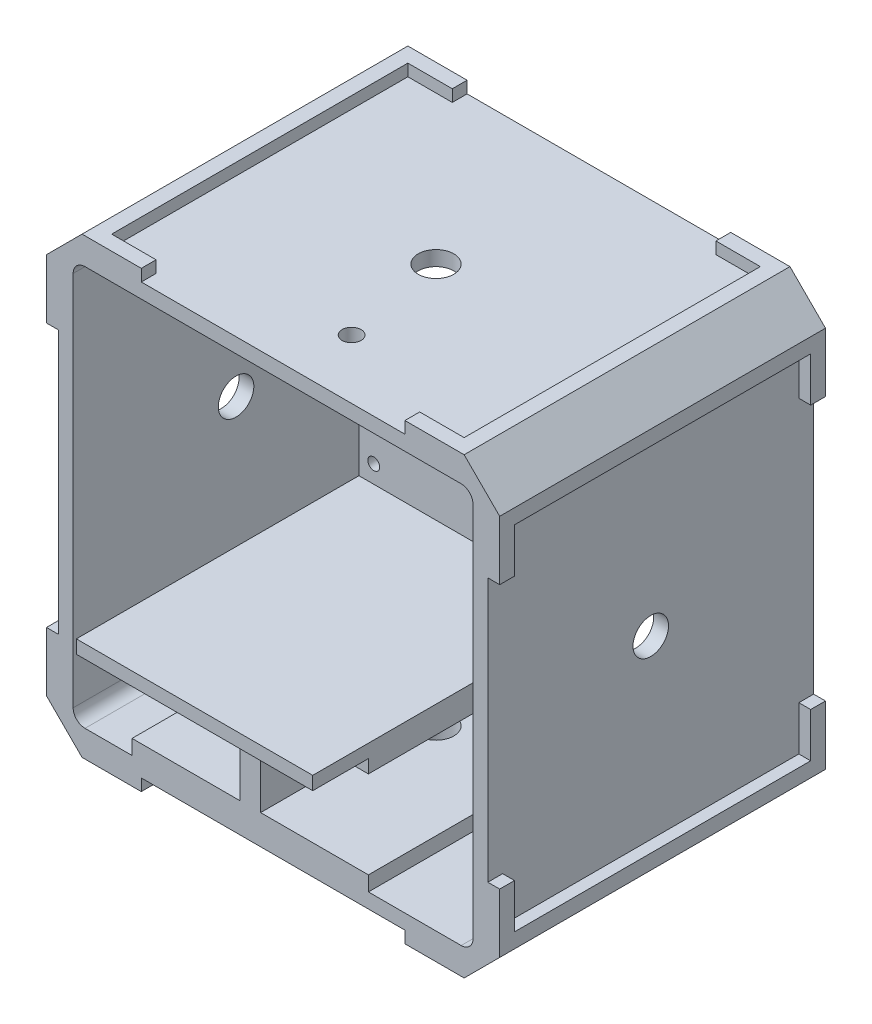
SolidWorks part; units mm, degrees
ref_plane "Front Plane" through (0, 0, 0) normal (0, 0, 1) x (1, 0, 0)
ref_plane "Top Plane" through (0, 0, 0) normal (0, 1, 0) x (1, 0, 0)
ref_plane "Right Plane" through (0, 0, 0) normal (1, 0, 0) x (0, 0, -1)
sketch "Sketch1" plane through (0, 0, 0) normal (0, 0, 1) x (1, 0, 0)
  line L0 (-33.75, -33.75) -> (33.75, -33.75) construction
  line L1 (-31.75, 33.75) -> (31.75, 33.75)
  line L2 (-33.75, 31.75) -> (-33.75, -31.75)
  line L3 (-31.75, -33.75) -> (31.75, -33.75)
  line L4 (33.75, 31.75) -> (33.75, -31.75)
  line L5 (-36.25, 32.25) -> (-36.25, -32.25)
  line L6 (33.75, 33.75) -> (33.75, -33.75) construction
  line L7 (-32.25, -36.25) -> (32.25, -36.25)
  line L8 (36.25, 32.25) -> (36.25, -32.25)
  line L9 (-32.25, 36.25) -> (32.25, 36.25)
  line L10 (-36.25, 36.25) -> (-36.25, -36.25) construction
  line L11 (-36.25, 36.25) -> (36.25, 36.25) construction
  line L12 (-33.75, 33.75) -> (33.75, 33.75) construction
  line L13 (-33.75, 33.75) -> (-33.75, -33.75) construction
  line L14 (-36.25, -36.25) -> (36.25, -36.25) construction
  line L15 (36.25, 36.25) -> (36.25, -36.25) construction
  line L16 (55, 0) -> (-55, 0) construction
  line L17 (0, -55) -> (0, 55) construction
  arc A0 (-36.25, 32.25) -> (-32.25, 36.25) centre (-32.25, 32.25) cw
  arc A1 (-31.75, 33.75) -> (-33.75, 31.75) centre (-31.75, 31.75) ccw
  arc A2 (-33.75, -31.75) -> (-31.75, -33.75) centre (-31.75, -31.75) ccw
  arc A3 (31.75, -33.75) -> (33.75, -31.75) centre (31.75, -31.75) ccw
  arc A4 (31.75, 33.75) -> (33.75, 31.75) centre (31.75, 31.75) cw
  arc A5 (-36.25, -32.25) -> (-32.25, -36.25) centre (-32.25, -32.25) ccw
  arc A6 (32.25, -36.25) -> (36.25, -32.25) centre (32.25, -32.25) ccw
  arc A7 (36.25, 32.25) -> (32.25, 36.25) centre (32.25, 32.25) ccw
  point P36 (-33.75, 0)
  point P39 (0, 33.75)
  dimension "D3" = 4
  dimension "D4" = 2
  dimension "D5" = 2
  dimension "D6" = 4
  dimension "D1" = 67.5
  dimension "D2" = 2.5
extrude "Boss-Extrude1" add sketch "Sketch1" along normal blind 55
sketch "Sketch2" plane through (0, 0, 0) normal (0, 0, 1) x (1, 0, 0)
  line L1 (-33.75, 33.75) -> (33.75, 33.75)
  line L2 (-33.75, 33.75) -> (-33.75, -33.75)
  line L3 (-33.75, -33.75) -> (33.75, -33.75)
  line L4 (33.75, 33.75) -> (33.75, -33.75)
extrude "Boss-Extrude2" add sketch "Sketch2" along normal blind 2.5
sketch "Sketch3" plane through (0, 0, 2.5) normal (0, 0, 1) x (1, 0, 0)
  line L0 (-4.38, 17.29) -> (-18.88, 12.29) construction
  line L1 (-19.88, 11.29) -> (-3.38, 11.29)
  line L2 (-18.88, 12.29) -> (-4.38, 12.29) construction
  line L3 (-18.88, 12.29) -> (-18.88, 17.29) construction
  line L4 (-18.88, 17.29) -> (-4.38, 17.29) construction
  line L5 (-4.38, 12.29) -> (-4.38, 17.29) construction
  line L6 (-3.38, 11.29) -> (-3.38, 18.29)
  line L7 (-19.88, 18.29) -> (-3.38, 18.29)
  line L8 (-19.88, 11.29) -> (-19.88, 18.29)
  line L9 (-36.25, 32.25) -> (-36.25, -32.25) construction
  line L10 (-3, -7) -> (3, -7) construction
  line L11 (-3, -7) -> (-3, 7) construction
  line L12 (-3, 7) -> (3, 7) construction
  line L13 (3, -7) -> (3, 7) construction
  line L14 (-3, -7) -> (3, 7) construction
  line L15 (-3, 7) -> (3, -7) construction
  line L16 (32.25, 36.25) -> (-32.25, 36.25) construction
  line L17 (-4, -8) -> (-4, 8)
  line L18 (-4, 8) -> (4, 8)
  line L19 (4, -8) -> (4, 8)
  line L20 (-4, -8) -> (4, -8)
  line L21 (-18.88, 17.29) -> (-4.38, 12.29) construction
  point P0 (0, 0)
  dimension "D2" = 6
  dimension "D3" = 14
  dimension "D5" = 14.5
  dimension "D6" = 5
  dimension "D7" = 16.37
  dimension "D8" = 23.96
  dimension "D1" = 1
  dimension "D4" = 1
extrude "Cut-Extrude1" cut sketch "Sketch3" against normal up to next
fillet "Fillet1" radius 1 8 edges at (-19.88, 11.29, 1.25) (-19.88, 18.29, 1.25) (-3.38, 18.29, 1.25) (-3.38, 11.29, 1.25) (4, -8, 1.25) (-4, -8, 1.25) (-4, 8, 1.25) (4, 8, 1.25)
sketch "Sketch4" plane through (0, 0, 0) normal (0, 0, -1) x (-1, 0, 0)
  line L0 (-32.25, 36.25) -> (32.25, 36.25) construction
  line L1 (-36.25, -32.25) -> (-36.25, 32.25) construction
  circle A0 centre (-28.75, 28.75) radius 1.5
  dimension "D3" = 3
  dimension "D1" = 7.5
  dimension "D2" = 7.5
extrude "Cut-Extrude2" cut sketch "Sketch4" against normal up to next
mirror "Mirror1" about plane through (0, 0, 0) normal (1, 0, 0) of "Cut-Extrude2"
mirror "Mirror2" about plane through (0, 0, 0) normal (0, 1, 0) of "Mirror1"
sketch "Sketch5" plane through (0, 0, 0) normal (1, 0, 0) x (0, 0, -1)
  line L2 (-16.7, 12) -> (-16.7, -12)
  line L3 (-16.7, -12) -> (-62.4, -12)
  line L6 (-14.7, -14) -> (-64.4, -14)
  line L7 (-14.7, 12) -> (-14.7, -14)
  line L9 (-62.4, -12) -> (-64.4, -12)
  line L10 (-64.4, -12) -> (-64.4, -14)
  line L11 (-62.4, 12) -> (-62.4, -12) construction
  line L12 (-64.4, 14) -> (-64.4, -14) construction
  line L15 (-16.7, 12) -> (-14.7, 12)
  line L16 (-14.7, 14) -> (-14.7, -14) construction
  line L17 (-14.7, 14) -> (-64.4, 14) construction
  line L18 (-16.7, 12) -> (-62.4, 12) construction
  point P4 (0, 0)
  dimension "D1" = 24
  dimension "D2" = 49.7
  dimension "D3" = 2
extrude "Boss-Extrude3" add sketch "Sketch5" along normal blind 16.09 and the other way blind 23.81 separate body
sketch "Sketch6" plane through (0, 0, 64.4) normal (0, 0, 1) x (1, 0, 0)
  line L0 (-23.81, -14) -> (16.09, -14) construction
  line L1 (-23.81, -14) -> (16.09, -14)
  line L2 (-23.81, -14) -> (-23.81, -16.5)
  line L3 (-23.81, -16.5) -> (-5.61, -16.5)
  line L4 (16.09, -14) -> (16.09, -16.5)
  line L5 (-31.75, -33.75) -> (31.75, -33.75) construction
  line L6 (-23.81, -33.75) -> (16.09, -33.75)
  line L7 (-23.81, -33.75) -> (-23.81, -31.25)
  line L8 (-23.81, -31.25) -> (-5.61, -31.25)
  line L9 (16.09, -33.75) -> (16.09, -31.25)
  line L10 (-2.11, -16.5) -> (16.09, -16.5)
  line L12 (-5.61, -16.5) -> (-5.61, -31.25)
  line L14 (-2.11, -16.5) -> (-2.11, -31.25)
  line L15 (-2.11, -31.25) -> (16.09, -31.25)
  line L16 (-23.81, -12) -> (-23.81, -14) construction
  dimension "D1" = 2.5
  dimension "D2" = 2.5
  dimension "D3" = 39.9
  dimension "D4" = 39.9
  dimension "D5" = 3.5
  dimension "D6" = 18.2
  dimension "D7" = 18.2
extrude "Boss-Extrude4" add sketch "Sketch6" against normal blind 47
sketch "Sketch7" plane through (0, 0, 64.4) normal (0, 0, 1) x (1, 0, 0)
  line L0 (-23.81, -12) -> (-23.81, -16.5) construction
  line L1 (-23.81, -14.25) -> (16.09, -14.25)
  line L2 (-23.81, -14.25) -> (-23.81, -33.75)
  line L3 (-23.81, -33.75) -> (16.09, -33.75)
  line L4 (16.09, -14.25) -> (16.09, -33.75)
  line L5 (16.09, -33.75) -> (31.75, -33.75) construction
  line L6 (16.09, -33.75) -> (16.09, -31.25) construction
extrude "Cut-Extrude3" cut sketch "Sketch7" against normal blind 9.4
sketch "Sketch9" [suppressed] plane through (-15.56, 0, 0) normal (-1, 0, 0) x (0, 0, 1)
  circle A0 centre (22.3967, 9) radius 1
  circle A1 centre (22.3967, 9) radius 2
  dimension "D1" = 2
  dimension "D2" = 1
extrude "Boss-Extrude6" [suppressed] add sketch "Sketch9" along normal blind 1.5
ref_plane "Plane1" through (-9.11, 0, 0) normal (-1, 0, 0) x (0, 0, 1)
sketch "Sketch10" [suppressed] plane through (-36.25, 0, 0) normal (-1, 0, 0) x (0, 0, 1)
  circle A0 centre (22.3967, 9) radius 1.5
  circle A1 centre (22.3967, -9) radius 1.5
  dimension "D1" = 3
  dimension "D2" = 3
extrude "Cut-Extrude4" [suppressed] cut sketch "Sketch10" against normal through all
sketch "Sketch12" plane through (0, 36.25, 0) normal (0, 1, 0) x (1, 0, 0)
  line L0 (-32.25, -55) -> (-32.25, 0) construction
  line L1 (32.25, -55) -> (29.75, -55)
  line L2 (32.25, -55) -> (32.25, -45)
  line L3 (32.25, -45) -> (29.75, -45)
  line L4 (29.75, -52.5) -> (29.75, -45)
  line L5 (32.25, -55) -> (22.25, -55)
  line L6 (32.25, -55) -> (32.25, -52.5)
  line L7 (29.75, -52.5) -> (22.25, -52.5)
  line L8 (22.25, -55) -> (22.25, -52.5)
  line L10 (-32.25, 0) -> (-32.25, -10)
  line L11 (-32.25, -10) -> (-29.75, -10)
  line L12 (-29.75, -2.5) -> (-29.75, -10)
  line L13 (-32.25, 0) -> (-22.25, 0)
  line L15 (-29.75, -2.5) -> (-22.25, -2.5)
  line L16 (-22.25, 0) -> (-22.25, -2.5)
  line M6 (-32.25, -55) -> (32.25, -55)
  line M7 (32.25, -55) -> (32.25, 0)
  dimension "D1" = 2.5
  dimension "D2" = 10
  dimension "D3" = 2.5
  dimension "D4" = 10
  dimension "D5" = 2.5
extrude "Boss-Extrude7" add sketch "Sketch12" along normal blind 2 contours L8 L2 L3 L4 L7 M6 M7 | L10 L11 L12 L15 L16 L13 region at (31, 36.25, 54.8586)
sketch "Sketch13" plane through (0, 0, 0) normal (0, 0, -1) x (-1, 0, 0)
  line L3 (-33.75, 21.25) -> (-25.25, 21.25)
  line L4 (-21.25, 33.75) -> (-21.25, 25.25)
  line L6 (0, 35.42) -> (0, -35.42) construction
  line L8 (21.25, 33.75) -> (21.25, 25.25)
  line L9 (33.75, 21.25) -> (25.25, 21.25)
  line L12 (35.42, 0) -> (-35.42, 0) construction
  line L17 (33.75, -21.25) -> (25.25, -21.25)
  line L18 (21.25, -33.75) -> (21.25, -25.25)
  line L19 (-21.25, -33.75) -> (-21.25, -25.25)
  line L20 (-33.75, -21.25) -> (-25.25, -21.25)
  line L27 (-33.75, 21.25) -> (-33.75, -21.25)
  line L29 (33.75, 21.25) -> (33.75, -21.25)
  line L34 (-21.25, 33.75) -> (21.25, 33.75)
  line L36 (-21.25, -33.75) -> (21.25, -33.75)
  arc A2 (-25.25, 21.25) -> (-21.25, 25.25) centre (-25.25, 25.25) ccw
  arc A4 (25.25, 21.25) -> (21.25, 25.25) centre (25.25, 25.25) cw
  arc A7 (25.25, -21.25) -> (21.25, -25.25) centre (25.25, -25.25) ccw
  arc A8 (-25.25, -21.25) -> (-21.25, -25.25) centre (-25.25, -25.25) cw
  dimension "D3" = 4
extrude "Cut-Extrude6" cut sketch "Sketch13" against normal up to next and the other way through all
sketch "Sketch15" plane through (0, 36.25, 0) normal (0, 1, 0) x (1, 0, 0)
  line L0 (22.25, -55) -> (-32.25, -55) construction
  line L1 (33.75, -55) -> (33.75, -2.5) construction
  circle A0 centre (3.25, -45) radius 1.6
  dimension "D1" = 3.2
  dimension "D2" = 10
  dimension "D3" = 30.5
extrude "Cut-Extrude8" cut sketch "Sketch15" against normal up to surface (2.5 mm away) and the other way through all up to face at (0, 33.75, 15)
sketch "Sketch16" plane through (-33.75, 0, 0) normal (1, 0, 0) x (0, 0, -1)
  line L2 (-16, 32.15) -> (-16, 29.65)
  line L7 (-16, 29.65) -> (-8.5, 29.65)
  line L9 (-16, 32.15) -> (-8.5, 32.15)
  line L10 (-8.5, 29.65) -> (-8.5, 32.15)
  line L12 (0, -32.25) -> (0, 32.25) construction
  dimension "D1" = 7.5
  dimension "D3" = 16
extrude "Boss-Extrude8" add sketch "Sketch16" along normal blind 7
sketch "Sketch17" plane through (0, 0, 14.7) normal (0, 0, -1) x (-1, 0, 0)
  line L0 (-16.09, -14) -> (-16.09, 12) construction
  line L2 (23.81, -14) -> (23.81, 12) construction
  line L3 (23.81, 12) -> (-16.09, 12) construction
  circle A0 centre (-13.59, 9) radius 1
  circle A1 centre (-13.59, -9) radius 1
  circle A2 centre (21.31, -9) radius 1
  point P12 (0, 0)
  dimension "D1" = 2
  dimension "D2" = 2.5
  dimension "D3" = 3
  dimension "D4" = 2.5
  dimension "D6" = 18
extrude "Cut-Extrude9" cut sketch "Sketch17" against normal up to next
sketch "Sketch19" plane through (0, 36.25, 0) normal (0, 1, 0) x (1, 0, 0)
  line L0 (32.25, -55) -> (-32.25, 0) construction
  line L1 (-32.25, 0) -> (-22.25, 0) construction
  line L2 (32.25, 0) -> (-32.25, -55) construction
  line L3 (32.25, -45) -> (32.25, 0) construction
  line L4 (32.25, 0) -> (-22.25, 0) construction
  line L5 (-32.25, 0) -> (-32.25, -10) construction
  line L6 (-32.25, 0) -> (-32.25, -10) construction
  circle A0 centre (0, -27.5) radius 3
  dimension "D1" = 6
extrude "Cut-Extrude10" cut sketch "Sketch19" against normal blind 2.5
sketch "Sketch20" plane through (36.25, 0, -36.25) normal (-1, 0, 0) x (0, 0, 1)
  line L0 (36.25, -32.25) -> (36.25, 32.25) construction
  line L1 (36.25, -32.25) -> (36.25, -22.25)
  line L2 (36.25, -32.25) -> (46.25, -32.25)
  line L3 (46.25, -32.25) -> (46.25, -29.75)
  line L4 (38.75, -29.75) -> (46.25, -29.75)
  line L5 (36.25, -32.25) -> (36.25, -22.25)
  line L7 (38.75, -29.75) -> (38.75, -22.25)
  line L8 (36.25, -22.25) -> (38.75, -22.25)
  line L10 (91.25, 32.25) -> (81.25, 32.25)
  line L11 (81.25, 32.25) -> (81.25, 29.75)
  line L12 (88.75, 29.75) -> (81.25, 29.75)
  line L13 (91.25, 32.25) -> (91.25, 22.25)
  line L15 (88.75, 29.75) -> (88.75, 22.25)
  line L16 (91.25, 22.25) -> (88.75, 22.25)
  line M25 (36.25, -32.25) -> (36.25, 32.25)
  line M26 (36.25, 32.25) -> (91.25, 32.25)
  line M27 (91.25, 32.25) -> (91.25, -32.25)
  line M28 (91.25, -32.25) -> (36.25, -32.25)
  dimension "D1" = 2.5
  dimension "D2" = 10
  dimension "D3" = 2.5
  dimension "D4" = 10
  dimension "D5" = 2.5
  dimension "D6" = 55
  dimension "D7" = 64.5
  dimension "D8" = 10
  dimension "D9" = 7.5
  dimension "D10" = 7.5
extrude "Boss-Extrude9" add sketch "Sketch20" against normal blind 2 contours L16 L15 L12 L11 M27 M26 | L8 L7 L4 L3 M25 M28 region at (36.25, -27.25, 0.1414) region at (36.25, 32.1086, 50)
ref_axis "Axis1" through (0, 0, 67.62) along (0, 0, -1)
pattern_circular "CirPattern1" count 4 every 90 about axis through (0, 0, 67.62) along (0, 0, -1) of "Boss-Extrude7", "Cut-Extrude10"
pattern_circular "CirPattern2" count 4 every 90 about axis through (0, 0, 67.62) along (0, 0, -1) of "Boss-Extrude9"
sketch "Sketch21" plane through (0, -33.75, 0) normal (0, -1, 0) x (1, 0, 0)
  line L0 (-2.11, 25.3674) -> (-2.11, 29.6326)
  arc A0 (-2.11, 25.3674) -> (-2.11, 29.6326) centre (0, 27.5) ccw
extrude "Cut-Extrude11" cut sketch "Sketch21" against normal blind 2.5
sketch "Sketch22" plane through (0, 0, 55) normal (0, 0, 1) x (1, 0, 0)
  line L0 (-38.25, 32.25) -> (-32.25, 38.25)
  line L1 (-32.25, 38.25) -> (-29.75, 38.25)
  line L8 (-29.75, 38.25) -> (-29.75, 33.75)
  line L13 (-38.25, 29.75) -> (-33.75, 29.75)
  line L20 (-38.25, 29.75) -> (-38.25, 32.25)
  line L24 (-32.25, 38.25) -> (-22.25, 38.25) construction
  line L26 (-33.75, 31.75) -> (-33.75, -31.75) construction
  line L27 (-38.25, 22.25) -> (-38.25, 32.25) construction
  line L28 (0, -35.42) -> (0, 35.42) construction
  line L29 (33.75, 33.75) -> (33.75, 29.75)
  line L30 (33.75, 33.75) -> (29.75, 33.75)
  line L31 (38.25, 29.75) -> (38.25, 32.25)
  line L32 (38.25, 29.75) -> (33.75, 29.75)
  line L33 (-33.75, 33.75) -> (-29.75, 33.75)
  line L34 (-33.75, 33.75) -> (-33.75, 29.75)
  line L37 (29.75, 38.25) -> (29.75, 33.75)
  line L38 (32.25, 38.25) -> (29.75, 38.25)
  line L39 (38.25, 32.25) -> (32.25, 38.25)
  line L40 (35.42, 0) -> (-35.42, 0) construction
  line L41 (38.25, -32.25) -> (32.25, -38.25)
  line L42 (32.25, -38.25) -> (29.75, -38.25)
  line L43 (29.75, -38.25) -> (29.75, -33.75)
  line L44 (-33.75, -33.75) -> (-33.75, -29.75)
  line L45 (-33.75, -33.75) -> (-29.75, -33.75)
  line L46 (38.25, -29.75) -> (33.75, -29.75)
  line L47 (38.25, -29.75) -> (38.25, -32.25)
  line L48 (33.75, -33.75) -> (29.75, -33.75)
  line L49 (33.75, -33.75) -> (33.75, -29.75)
  line L50 (-38.25, -29.75) -> (-38.25, -32.25)
  line L51 (-38.25, -29.75) -> (-33.75, -29.75)
  line L52 (-29.75, -38.25) -> (-29.75, -33.75)
  line L53 (-32.25, -38.25) -> (-29.75, -38.25)
  line L54 (-38.25, -32.25) -> (-32.25, -38.25)
  dimension "D1" = 2.5
  dimension "D2" = 2.5
extrude "Boss-Extrude12" add sketch "Sketch22" against normal through all
sketch "Sketch23" plane through (0, 0, 14.7) normal (0, 0, -1) x (-1, 0, 0)
  line L0 (23.81, 12) -> (-16.09, 12) construction
  line L1 (18.31, 12) -> (23.81, 12)
  line L2 (18.31, 12) -> (18.31, -4)
  line L3 (18.31, -4) -> (23.81, -4)
  line L4 (23.81, 12) -> (23.81, -4)
  line L5 (23.81, -14) -> (23.81, 12) construction
  circle A0 centre (21.31, -9) radius 1 construction
  dimension "D1" = 5
  dimension "D2" = 5.5
extrude "Cut-Extrude12" cut sketch "Sketch23" against normal up to next
sketch "Sketch24" plane through (16.09, 0, 0) normal (1, 0, 0) x (0, 0, -1)
  line L0 (-14.7, -14) -> (-14.7, 12) construction
  line L1 (-17.4, -16.5) -> (-17.4, -13.792)
  line L2 (-17.4, -13.792) -> (-14.7, -14)
  arc A0 (-14.7, -14) -> (-17.4, -16.5) centre (-17.4, -13.792) cw
  point P3 (-17.4, -13.751)
  point P7 (-17.4824, -16.5)
  point P8 (-14.7, -14)
  point P10 (-17.4, -13.792)
extrude "Boss-Extrude13" add sketch "Sketch24" against normal up to surface (39.9 mm away) up to face at (-23.81, -12.15, 33.64)
fillet "Fillet2" radius 1.5 1 edges at (16.09, 12, 15.7)
